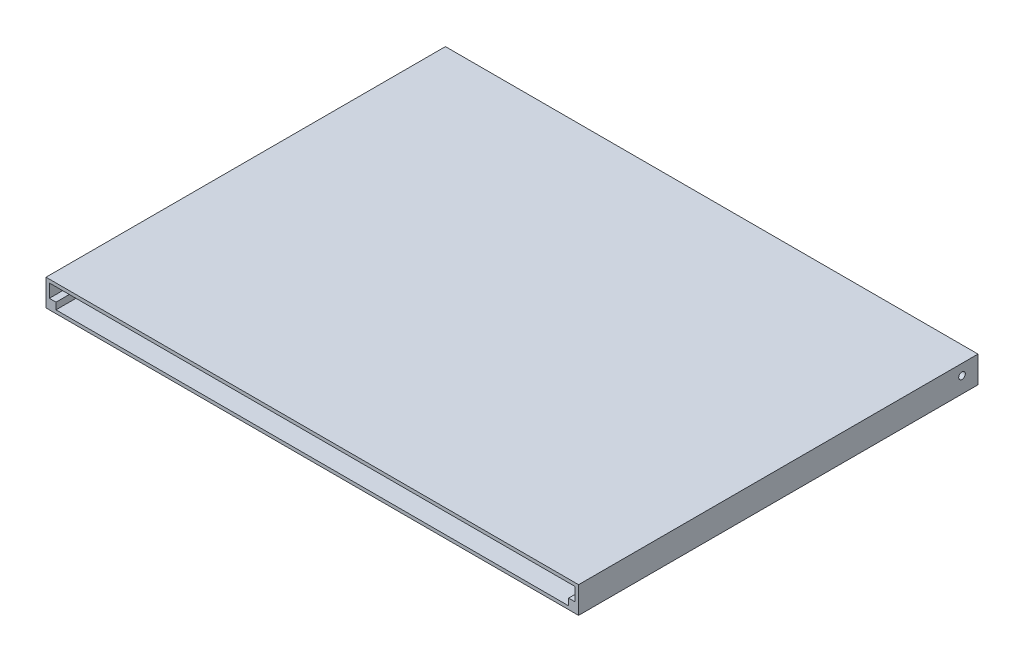
SolidWorks part; units mm, degrees
ref_plane "Front Plane" through (0, 0, 0) normal (0, 0, 1) x (1, 0, 0)
ref_plane "Top Plane" through (0, 0, 0) normal (0, 1, 0) x (1, 0, 0)
ref_plane "Right Plane" through (0, 0, 0) normal (1, 0, 0) x (0, 0, -1)
sketch "Sketch1" plane through (0, 0, 0) normal (0, 1, 0) x (1, 0, 0)
  line L1 (-254, 190.5) -> (254, 190.5)
  line L2 (-254, 190.5) -> (-254, -190.5)
  line L3 (-254, -190.5) -> (254, -190.5)
  line L4 (254, 190.5) -> (254, -190.5)
  line L5 (-254, 190.5) -> (254, -190.5) construction
  line L6 (-254, -190.5) -> (254, 190.5) construction
  point P0 (0, 0)
  dimension "D1" = 381
  dimension "D2" = 508
extrude "Boss-Extrude1" add sketch "Sketch1" along normal blind 25.4
sketch "Sketch2" plane through (0, 0, 190.5) normal (0, 0, 1) x (1, 0, 0)
  line L0 (-254, 25.4) -> (-254, 0) construction
  line L1 (250.825, 22.225) -> (-250.825, 22.225)
  line L2 (250.825, 22.225) -> (250.825, 3.175)
  line L3 (250.825, 3.175) -> (-250.825, 3.175)
  line L4 (-250.825, 22.225) -> (-250.825, 3.175)
  line L5 (250.825, 22.225) -> (-250.825, 3.175) construction
  line L6 (250.825, 3.175) -> (-250.825, 22.225) construction
  line L7 (254, 25.4) -> (254, 0) construction
  line L8 (-254, 25.4) -> (254, 25.4) construction
  line L9 (-254, 0) -> (254, 0) construction
  point P0 (0, 12.7)
  dimension "D1" = 3.175
  dimension "D2" = 3.175
  dimension "D3" = 3.175
  dimension "D4" = 3.175
extrude "Cut-Extrude1" cut sketch "Sketch2" against normal blind 342.9
sketch "Sketch3" plane through (0, 0, 190.5) normal (0, 0, 1) x (1, 0, 0)
  line L0 (0, -55) -> (0, 55) construction
  line L1 (-250.825, 9.525) -> (-244.475, 9.525)
  line L2 (-250.825, 9.525) -> (-250.825, 3.175)
  line L3 (-250.825, 3.175) -> (-244.475, 3.175)
  line L4 (-244.475, 9.525) -> (-244.475, 3.175)
  line L13 (250.825, 3.175) -> (244.475, 3.175)
  line L14 (244.475, 9.525) -> (244.475, 3.175)
  line L15 (250.825, 9.525) -> (244.475, 9.525)
  line L16 (250.825, 9.525) -> (250.825, 3.175)
  dimension "D1" = 6.35
  dimension "D2" = 6.35
extrude "Boss-Extrude2" add sketch "Sketch3" against normal blind 35.56
sketch "Sketch4" plane through (-254, 0, 0) normal (-1, 0, 0) x (0, 0, 1)
  line L2 (-190.5, 0) -> (190.5, 0) construction
  line L3 (190.5, 25.4) -> (190.5, 0) construction
  circle A0 centre (-175.26, 15.24) radius 3.175
  dimension "D1" = 6.35
  dimension "D2" = 15.24
  dimension "D3" = 365.76
extrude "Cut-Extrude2" cut sketch "Sketch4" against normal blind 25.4
extrude "Cut-Extrude3" cut sketch "Sketch4<2>" along normal blind 25.4 from surface starting at face at (254, 12.7, 0)
sketch "Sketch4<2>" plane through (-254, 0, 0) normal (-1, 0, 0) x (0, 0, 1) same geometry as "Sketch4"
